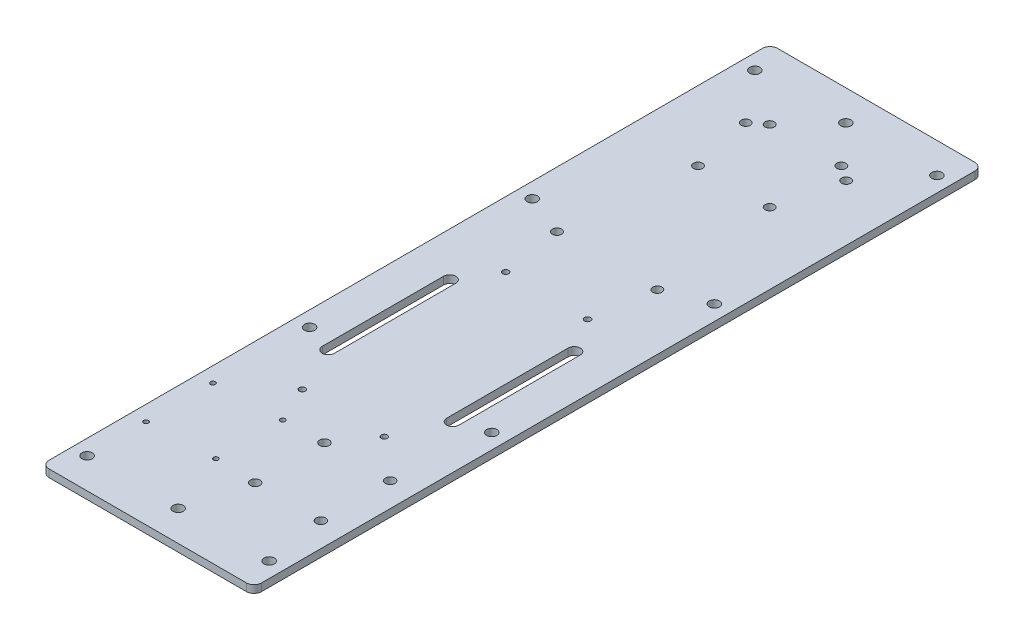
SolidWorks part; units mm, degrees
ref_plane "Front Plane" through (0, 0, 0) normal (0, 0, 1) x (1, 0, 0)
ref_plane "Top Plane" through (0, 0, 0) normal (0, 1, 0) x (1, 0, 0)
ref_plane "Right Plane" through (0, 0, 0) normal (1, 0, 0) x (0, 0, -1)
sketch "Sketch2" plane through (0, 0, 0) normal (0, 1, 0) x (1, 0, 0)
  line L0 (-44.45, 0) -> (44.45, 0) construction
  line L1 (-41.275, 152.4) -> (41.275, 152.4)
  line L2 (-44.45, 149.225) -> (-44.45, -149.225)
  line L3 (-41.275, -152.4) -> (41.275, -152.4)
  line L4 (44.45, 149.225) -> (44.45, -149.225)
  line L5 (0, 152.4) -> (0, -152.4) construction
  arc A0 (-44.45, -149.225) -> (-41.275, -152.4) centre (-41.275, -149.225) ccw
  arc A1 (41.275, -152.4) -> (44.45, -149.225) centre (41.275, -149.225) ccw
  arc A2 (41.275, 152.4) -> (44.45, 149.225) centre (41.275, 149.225) cw
  arc A3 (-41.275, 152.4) -> (-44.45, 149.225) centre (-41.275, 149.225) ccw
  point P8 (0, 0)
  point P13 (-44.45, -152.4)
  point P16 (44.45, -152.4)
  point P21 (-44.45, 152.4)
  dimension "D3" = 3.175
  dimension "D1" = 304.8
  dimension "D2" = 88.9
extrude "Plate Thickness" add sketch "Sketch2" along normal blind 3.175 contours L2 A0 L3 A1 L4 A2 L1 A3
sketch "Sketch3" plane through (0, 3.175, 0) normal (0, 1, 0) x (1, 0, 0)
  line L0 (-44.45, 149.225) -> (-44.45, -149.225) construction
  line L1 (-41.275, 152.4) -> (41.275, 152.4) construction
  line L4 (0, 152.4) -> (0, -152.4) construction
  line L5 (-41.275, -152.4) -> (41.275, -152.4) construction
  line L6 (-41.275, -152.4) -> (41.275, -152.4) construction
  circle A0 centre (-38.1, 139.7) radius 2.159
  circle A1 centre (-38.1, 46.5667) radius 2.159
  circle A2 centre (-38.1, -46.5667) radius 2.159
  circle A3 centre (-38.1, -139.7) radius 2.159
  circle A4 centre (38.1, -139.7) radius 2.159
  circle A5 centre (38.1, -46.5667) radius 2.159
  circle A6 centre (38.1, 46.5667) radius 2.159
  circle A7 centre (38.1, 139.7) radius 2.159
  circle A8 centre (0, 139.7) radius 2.159
  circle A9 centre (0, -139.7) radius 2.159
  dimension "D1" = 4.318
  dimension "D4" = 4.318
  dimension "D2" = 6.35
  dimension "D3" = 12.7
  dimension "D5" = 12.7
  dimension "D6" = 12.7
  dimension "D7" = 93.1333
  dimension "D8" = 93.1333
extrude "Mounting holes" cut sketch "Sketch3" against normal through all
sketch "Sketch4" plane through (0, 3.175, 0) normal (0, 1, 0) x (1, 0, 0)
  line L0 (-21.0058, 39.8143) -> (21.0058, 39.8143) construction
  line L1 (0, 0) -> (0, 139.7) construction
  circle A0 centre (-21.0058, 118.8083) radius 1.905
  circle A1 centre (-21.0058, 39.8143) radius 1.905
  circle A2 centre (21.0058, 39.8143) radius 1.905
  circle A3 centre (21.0058, 118.8083) radius 1.905
  point P13 (0, 39.8143)
  point P17 (0, 69.85)
  point P18 (0, 69.85)
  dimension "D1" = 3.81
  dimension "D2" = 78.994
  dimension "D3" = 42.0116
extrude "Jetson Holes (w/o mount)" cut sketch "Sketch4" against normal through all
sketch "Sketch5" plane through (0, 3.175, 0) normal (0, 1, 0) x (1, 0, 0)
  line L0 (-41.275, 152.4) -> (41.275, 152.4) construction
  line L1 (44.45, 149.225) -> (44.45, -149.225) construction
  circle A1 centre (-15.3784, 123.19) radius 1.905
  circle A3 centre (14.619, 123.19) radius 1.905
  circle A4 centre (14.619, 93.1926) radius 1.905
  circle A5 centre (-15.3784, 93.1926) radius 1.905
  point P12 (14.619, 116.2839)
  dimension "D1" = 3.81
  dimension "D2" = 29.9974
  dimension "D4" = 29.21
  dimension "D5" = 29.831
  dimension "D3" = 29.9974
extrude "PDB holes" cut sketch "Sketch5" against normal through all
sketch "Sketch6" plane through (0, 3.175, 0) normal (0, 1, 0) x (1, 0, 0)
  circle A6 centre (37.9835, -101.7966) radius 1.905
  circle A7 centre (17.9175, -81.7306) radius 1.905
  circle A8 centre (17.9175, -121.8626) radius 1.905
  dimension "D5" = 3.81
  dimension "D6" = 40.132
  dimension "D7" = 20.066
  dimension "D8" = 20.066
extrude "Lidar Holes" [suppressed] cut sketch "Sketch6" against normal through all
sketch "Sketch7" plane through (0, 3.175, 0) normal (0, 1, 0) x (1, 0, 0)
  line L0 (0, 152.4) -> (0, -152.4) construction
  line L1 (-41.275, 152.4) -> (41.275, 152.4) construction
  line L2 (-41.275, -152.4) -> (41.275, -152.4) construction
  line L3 (17.145, 14.4893) -> (-17.145, 14.4893) construction
  circle A0 centre (-17.145, 14.4893) radius 1.27
  circle A1 centre (-17.145, -70.6007) radius 1.27
  circle A2 centre (17.145, -70.6007) radius 1.27
  circle A3 centre (17.145, 14.4893) radius 1.27
  point P14 (0, 14.4893)
  dimension "D1" = 2.54
  dimension "D2" = 85.09
  dimension "D3" = 34.29
extrude "PixHawk Holes" cut sketch "Sketch7" against normal through all
sketch "Sketch8" plane through (0, 3.175, 0) normal (0, 1, 0) x (1, 0, 0)
  line L0 (0, 152.4) -> (0, -115.5095) construction
  line L1 (-41.275, 152.4) -> (41.275, 152.4) construction
  line L2 (-26.035, -0.006) -> (-26.035, -50.806) construction
  line L3 (-23.495, -0.006) -> (-23.495, -50.806)
  line L4 (-28.575, -0.006) -> (-28.575, -50.806)
  line L5 (26.035, -0.006) -> (26.035, -50.806) construction
  line L6 (23.495, -0.006) -> (23.495, -50.806)
  line L7 (28.575, -0.006) -> (28.575, -50.806)
  arc A0 (-23.495, -0.006) -> (-28.575, -0.006) centre (-26.035, -0.006) ccw
  arc A1 (-28.575, -50.806) -> (-23.495, -50.806) centre (-26.035, -50.806) ccw
  arc A2 (23.495, -0.006) -> (28.575, -0.006) centre (26.035, -0.006) cw
  arc A3 (28.575, -50.806) -> (23.495, -50.806) centre (26.035, -50.806) cw
  point P7 (-26.035, -25.406)
  point P14 (26.035, -25.406)
  dimension "D1" = 50.8
  dimension "D2" = 5.08
  dimension "D3" = 26.035
extrude "Battery Holes" cut sketch "Sketch8" against normal through all
sketch "Sketch9" plane through (0, 3.175, 0) normal (0, 1, 0) x (1, 0, 0)
  line L0 (44.45, 149.225) -> (44.45, -149.225) construction
  line L1 (-41.275, -152.4) -> (41.275, -152.4) construction
  circle A0 centre (6.8334, -85.3) radius 2
  circle A1 centre (34.3334, -85.3) radius 2
  circle A2 centre (34.3334, -114.3) radius 2
  circle A3 centre (6.8334, -114.3) radius 2
  dimension "D1" = 4
  dimension "D3" = 10.1166
  dimension "D5" = 38.1
  dimension "D2" = 27.5
  dimension "D4" = 29
extrude "Cut-Extrude1" cut sketch "Sketch9" against normal through all
sketch "Sketch10" plane through (0, 3.175, 0) normal (0, 1, 0) x (1, 0, 0)
  line L0 (-44.45, 149.225) -> (-44.45, -149.225) construction
  circle A0 centre (-38.1255, -87.0086) radius 1
  circle A1 centre (-38.1, -115.0086) radius 1
  circle A2 centre (-10.1266, -85.7891) radius 1
  circle A3 centre (-10.1266, -113.7891) radius 1
  dimension "D1" = 2
  dimension "D2" = 28
  dimension "D3" = 28
  dimension "D4" = 28
  dimension "D5" = 6.35
extrude "Ventral Camera holes" cut sketch "Sketch10" against normal up to next
